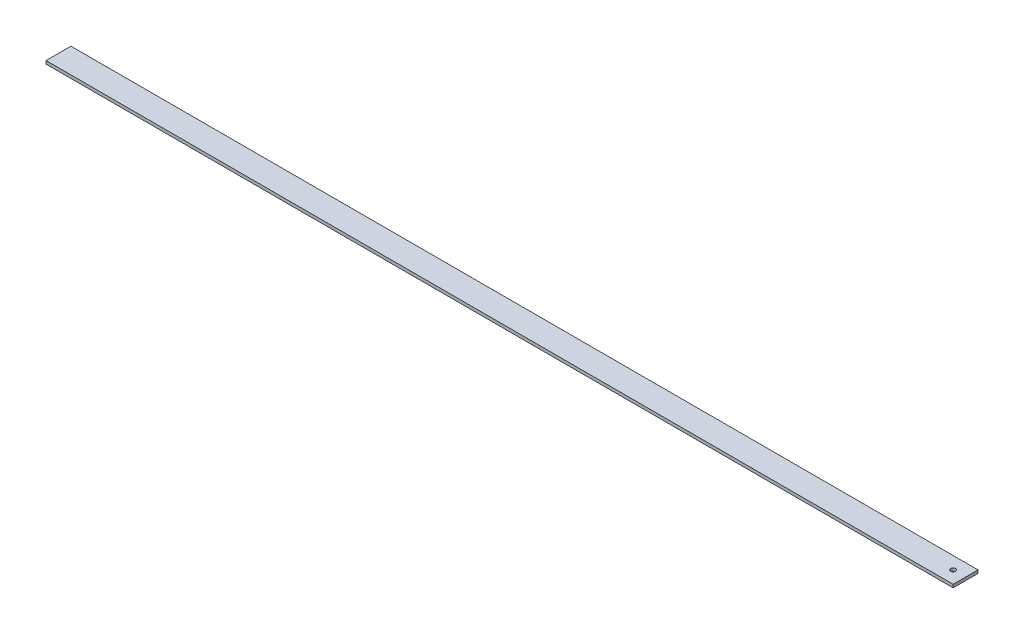
SolidWorks part; units mm, degrees
ref_plane "Alzado" through (0, 0, 0) normal (0, 0, 1) x (1, 0, 0)
ref_plane "Planta" through (0, 0, 0) normal (0, 1, 0) x (1, 0, 0)
ref_plane "Vista lateral" through (0, 0, 0) normal (1, 0, 0) x (0, 0, -1)
sketch "Croquis1" plane through (0, 0, 0) normal (0, 1, 0) x (1, 0, 0)
  line L0 (1742.85, -198.9028) -> (1742.85, -249.7028)
  line L1 (1742.85, -249.7028) -> (-50.8, -249.7028)
  line L2 (-50.8, -249.7028) -> (-50.8, 0)
  line L3 (-50.8, 0) -> (0, 0)
  line L4 (0, 0) -> (0, -198.9028)
  line L5 (0, -198.9028) -> (1742.85, -198.9028)
  dimension "D1" = 1793.65
  dimension "D2" = 50.8
  dimension "D3" = 1742.85
  dimension "D4" = 249.7028
extrude "Saliente-Extruir1" add sketch "Croquis1" along normal blind 6.31
sketch "Croquis2" plane through (-50.8, 0, 0) normal (-1, 0, 0) x (0, 0, 1)
  line L0 (0, 6.31) -> (0, 132.55)
  line L1 (0, 132.55) -> (-32.5724, 197.8802)
  line L2 (6.31, 6.31) -> (6.31, 134.0358)
  line L3 (6.31, 134.0358) -> (-26.9254, 200.6957)
  line L4 (-32.5724, 197.8802) -> (-26.9254, 200.6957)
  line L5 (0, 6.31) -> (6.31, 6.31)
  dimension "D1" = 153.5
  dimension "D2" = 126.24
  dimension "D3" = 73
  dimension "D4" = 6.31
extrude "Saliente-Extruir2" add sketch "Croquis2" against normal blind 50.8
sketch "Croquis3" plane through (-50.8, 0, 0) normal (-1, 0, 0) x (0, 0, 1)
  line L0 (6.31, 6.31) -> (6.31, 134.0358) construction
  line L1 (6.31, 134.0358) -> (-26.9254, 200.6957) construction
  line L2 (6.41, 6.41) -> (6.41, 134.0594)
  line L3 (6.41, 134.0594) -> (-26.8359, 200.7403)
  line L4 (12.72, 6.41) -> (12.72, 135.5452)
  line L5 (12.72, 135.5452) -> (-21.1889, 203.5558)
  line L6 (-26.8359, 200.7403) -> (-21.1889, 203.5558)
  line L7 (6.41, 6.41) -> (12.72, 6.41)
  line L8 (6.31, 6.31) -> (249.7028, 6.31) construction
  line L10 (6.41, 6.31) -> (6.41, 134.0594) construction
  line L11 (12.72, 6.31) -> (12.72, 135.5452) construction
  dimension "D3" = 0.1
  dimension "D1" = 0.1
  dimension "D2" = 6.31
extrude "Saliente-Extruir3" add sketch "Croquis3" against normal blind 50.8 separate body
sketch "Croquis4" plane through (1742.85, 0, 0) normal (1, 0, 0) x (0, 0, -1)
  line L0 (-249.7028, 6.31) -> (-198.9028, 6.31)
  line L1 (-198.9028, 6.31) -> (-198.9028, 0)
  line L2 (-198.9028, 0) -> (-249.7028, 0)
  line L3 (-249.7028, 0) -> (-249.7028, 6.31)
extrude "Saliente-Extruir4" add sketch "Croquis4" along normal blind 50.8
sketch "Croquis6" plane through (0, 0, 0) normal (0, -1, 0) x (-1, 0, 0)
  line L0 (-882.5074, -174.7318) -> (-874.6021, -173.505) construction
  line L1 (-874.6021, -173.505) -> (-874.6021, -165.505) construction
  circle A0 centre (-874.6021, -173.505) radius 8 construction
  circle A1 centre (-874.6021, -173.505) radius 5
sketch "Croquis7" plane through (0, 0, 0) normal (0, -1, 0) x (-1, 0, 0)
  line L0 (-1774.7, -229.0653) -> (-1774.7, -224.3028) construction
  line L1 (-1774.7, -224.3028) -> (-1769.9375, -224.3028) construction
  circle A0 centre (-1774.7, -224.3028) radius 4.7625 construction
  circle A1 centre (-1774.7, -224.3028) radius 5
  dimension "D1" = 10
extrude "Cortar-Extruir3" cut sketch "Croquis7" against normal blind 50
sketch "Croquis8" plane through (0, 0, 12.72) normal (0, 0, 1) x (1, 0, 0)
  line L0 (-25.4, 6.31) -> (-25.4, 135.5452) construction
  line L1 (0, 6.31) -> (-50.8, 6.31) construction
  line L2 (0, 135.5452) -> (-50.8, 135.5452) construction
  line L3 (-25.4, 6.31) -> (0, 6.31) construction
  line L4 (0, 6.31) -> (-12.7, 6.31) construction
  line L5 (-12.7, 6.31) -> (-12.7, 36.91) construction
  line L6 (-12.7, 36.91) -> (-50.8, 36.91) construction
  line L7 (-50.8, 6.41) -> (-50.8, 135.5452) construction
  line L8 (-50.8, 36.91) -> (-25.4, 36.91) construction
  line L9 (-25.4, 36.91) -> (-38.1, 36.91) construction
  line L10 (-38.1, 36.91) -> (-38.1, 98.1) construction
  circle A0 centre (-38.1, 98.1) radius 5
  circle A1 centre (-12.7, 36.91) radius 5
  dimension "D3" = 10
  dimension "D4" = 10
  dimension "D1" = 30.6
  dimension "D2" = 61.19
extrude "Cortar-Extruir4" cut sketch "Croquis8" against normal blind 24
sketch "Croquis9" plane through (1793.65, 0, 0) normal (1, 0, 0) x (0, 0, -1)
  line L0 (-198.9028, 6.31) -> (-198.9028, 0)
  line L1 (-198.9028, 0) -> (-249.7028, 0)
  line L2 (-249.7028, 0) -> (-249.7028, 6.31)
  line L3 (-249.7028, 6.31) -> (-198.9028, 6.31)
extrude "Saliente-Extruir5" add sketch "Croquis9" along normal blind 6.45
sketch "Croquis11" plane through (0, 0, 12.72) normal (0, 0, 1) x (1, 0, 0)
  line L0 (-50.8, 6.41) -> (0, 6.31)
  line L1 (0, 6.31) -> (0, 211.9449)
  line L2 (0, 211.9449) -> (-50.8, 211.9449)
  line L3 (-50.8, 211.9449) -> (-50.8, 6.41)
extrude "Cortar-Extruir6" cut sketch "Croquis11" against normal blind 108
sketch "Croquis12" plane through (0, 6.31, 0) normal (0, 1, 0) x (1, 0, 0)
  line L0 (0, -198.9028) -> (-50.8, -198.9028)
  line L1 (-50.8, -6.31) -> (-50.8, -249.7028) construction
  line L2 (-50.8, -198.9028) -> (-50.8, 0)
  line L3 (-50.8, 0) -> (0, 0)
  line L4 (0, -198.9028) -> (0, 0)
extrude "Cortar-Extruir7" cut sketch "Croquis12" against normal blind 108 and the other way blind 108
